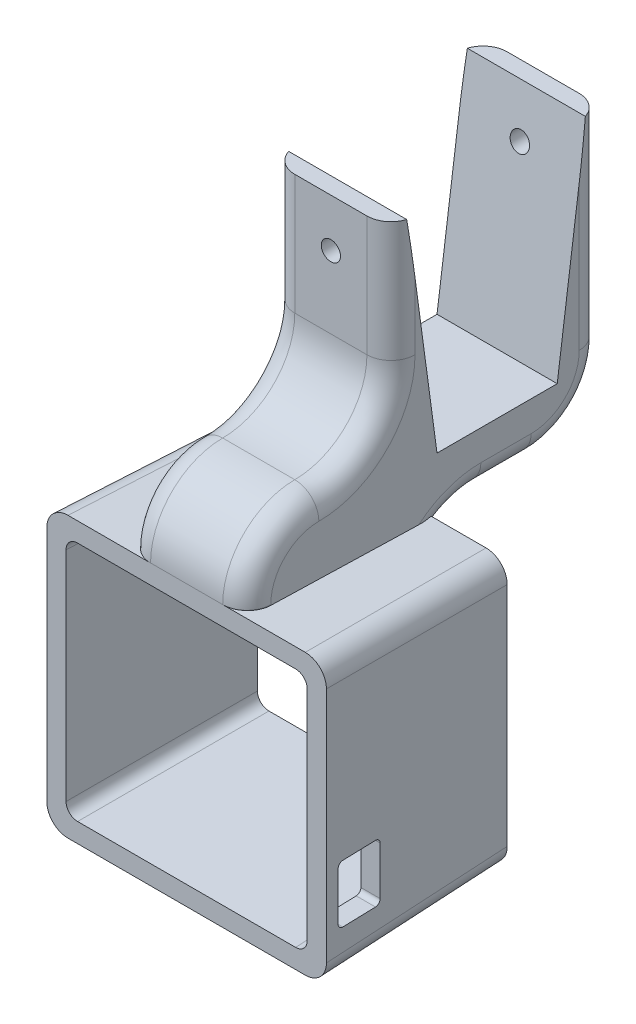
SolidWorks part; units mm, degrees
ref_plane "Front Plane" through (0, 0, 0) normal (0, 0, 1) x (1, 0, 0)
ref_plane "Top Plane" through (0, 0, 0) normal (0, 1, 0) x (1, 0, 0)
ref_plane "Right Plane" through (0, 0, 0) normal (1, 0, 0) x (0, 0, -1)
sketch "Sketch1" plane through (0, 0, 0) normal (0, 0, 1) x (1, 0, 0)
  line L0 (-27.975, -27.975) -> (-27.975, 27.975)
  line L1 (-23.975, -23.975) -> (23.975, -23.975)
  line L2 (-23.975, -23.975) -> (-23.975, 23.975)
  line L3 (-23.975, 23.975) -> (23.975, 23.975)
  line L4 (23.975, -23.975) -> (23.975, 23.975)
  line L5 (-23.975, -23.975) -> (23.975, 23.975) construction
  line L6 (-23.975, 23.975) -> (23.975, -23.975) construction
  line L7 (-27.975, 27.975) -> (27.975, 27.975)
  line L8 (27.975, -27.975) -> (27.975, 27.975)
  line L9 (-27.975, -27.975) -> (27.975, -27.975)
  point P0 (0, 0)
  dimension "D1" = 47.95
  dimension "D2" = 47.95
  dimension "D3" = 4
ref_plane "Plane1" through (0, 0, 38.7) normal (0, 0, 1) x (1, 0, 0)
sketch "Sketch2" plane through (0, 0, 38.7) normal (0, 0, 1) x (1, 0, 0)
  line L0 (-23.975, 23.975) -> (23.975, -23.975) construction
  line L1 (-25.075, -25.075) -> (25.075, -25.075)
  line L2 (-25.075, -25.075) -> (-25.075, 25.075)
  line L3 (-25.075, 25.075) -> (25.075, 25.075)
  line L4 (25.075, -25.075) -> (25.075, 25.075)
  line L5 (-25.075, -25.075) -> (25.075, 25.075) construction
  line L6 (-25.075, 25.075) -> (25.075, -25.075) construction
  line L7 (-29.075, 29.075) -> (29.075, 29.075)
  line L8 (29.075, -29.075) -> (29.075, 29.075)
  line L9 (-29.075, -29.075) -> (29.075, -29.075)
  line L10 (-29.075, -29.075) -> (-29.075, 29.075)
  point P0 (0, 0)
  dimension "D1" = 50.15
  dimension "D2" = 4
loft "Loft2" add section "Sketch1" section "Sketch2" connector at (-27.975, 27.975, 0) connector at (-29.075, 29.075, 38.7)
sketch "Sketch3" plane through (0, 0, 38.7) normal (0, 0, 1) x (1, 0, 0)
  line L14 (-25.075, -25.075) -> (25.075, -25.075)
  line L15 (25.075, -25.075) -> (25.075, 25.075)
  line L16 (25.075, 25.075) -> (-25.075, 25.075)
  line L17 (-25.075, 25.075) -> (-25.075, -25.075)
  line L18 (-25.075, -25.075) -> (25.075, -25.075)
  line L19 (25.075, -25.075) -> (25.075, 25.075)
  line L20 (25.075, 25.075) -> (-25.075, 25.075)
  line L21 (-25.075, 25.075) -> (-25.075, -25.075)
  dimension "D1" = 4
sketch "Sketch4" plane through (0, 0, 0) normal (0, 0, -1) x (-1, 0, 0)
  line L14 (-23.975, -23.975) -> (23.975, -23.975)
  line L15 (23.975, -23.975) -> (23.975, 23.975)
  line L16 (23.975, 23.975) -> (-23.975, 23.975)
  line L17 (-23.975, 23.975) -> (-23.975, -23.975)
  line L18 (-23.975, -23.975) -> (23.975, -23.975)
  line L19 (23.975, -23.975) -> (23.975, 23.975)
  line L20 (23.975, 23.975) -> (-23.975, 23.975)
  line L21 (-23.975, 23.975) -> (-23.975, -23.975)
  dimension "D1" = 4
loft "Cut-Loft1" cut profiles "Sketch4", "Sketch3" connector at (23.975, 23.975, 0) connector at (25.075, 25.075, 38.7)
fillet "Fillet1" radius 2.4 4 edges
fillet "Fillet2" radius 4.4 4 edges
sketch "Sketch5" plane through (0, 0, 0) normal (1, 0, 0) x (0, 0, -1)
  line L0 (-38.7, 31.9001) -> (-38.7, -31.9001) construction
  line L1 (-36.2, -8) -> (-27.2, -8)
  line L2 (-36.2, -8) -> (-36.2, -20)
  line L3 (-36.2, -20) -> (-27.2, -20)
  line L4 (-27.2, -8) -> (-27.2, -20)
  line L5 (-36.2, -8) -> (-27.2, -20) construction
  line L6 (-36.2, -20) -> (-27.2, -8) construction
  line L7 (-38.7, -29) -> (-47.7742, -29) construction
  point P0 (-31.7, -14)
  dimension "D1" = 2.5
  dimension "D2" = 11.5
  dimension "D3" = 29
  dimension "D4" = 9
  dimension "D5" = 21
extrude "Cut-Extrude1" cut sketch "Sketch5" along normal up to surface (28.7481 mm away) up to face at (28.525, -12.3384, 19.35)
fillet "Fillet3" radius 1 4 edges at (27.0039, -20, 36.2) (27.0039, -8, 36.2) (26.7481, -8, 27.2) (26.7481, -20, 27.2)
sketch "Sketch6" plane through (0, 0, 0) normal (1, 0, 0) x (0, 0, -1)
  line L0 (-38.7, 31.9826) -> (-38.7, -31.9826) construction
  line L1 (-8.7, 44.0797) -> (-8.7, 84.0797)
  line L2 (-8.7, 44.0797) -> (-38.7, 44.0797)
  line L3 (35.4525, 84.0797) -> (35.4525, 44.0797)
  line L4 (-38.7, 44.0797) -> (-38.7, 27.789)
  line L5 (0.8762, 39.0797) -> (25.8762, 39.0797)
  line L6 (-38.7, 27.789) -> (35.4525, 27.789)
  line L7 (0.8762, 39.0797) -> (-5.2, 84.0797)
  line L8 (35.4525, 27.789) -> (35.4525, 44.0797)
  line L10 (25.8762, 39.0797) -> (31.9525, 84.0797)
  line L11 (-8.7, 84.0797) -> (-5.2, 84.0797)
  line L12 (35.4525, 84.0797) -> (31.9525, 84.0797)
  dimension "D1" = 25
  dimension "D2" = 3.5
  dimension "D3" = 97.69
  dimension "D4" = 40
  dimension "D5" = 0
  dimension "D6" = 45
  dimension "D7" = 97.69
  dimension "D8" = 3.5
  dimension "D9" = 40
  dimension "D10" = 0
  dimension "D11" = 30
extrude "Boss-Extrude1" add sketch "Sketch6" along normal blind 12.5 and the other way blind 12.5
fillet "Fillet4" radius 15 4 edges at (0, 44.0797, 8.7) (0, 44.0797, 38.7) (0, 27.789, -35.4525) (0, 27.789, 0)
sketch "Sketch8" plane through (0, 0, 8.7) normal (0, 0, 1) x (1, 0, 0)
  line L0 (-12.5, 84.0797) -> (12.5, 84.0797) construction
  circle A0 centre (0, 74.0797) radius 2
  dimension "D2" = 4
  dimension "D1" = 10
extrude "Cut-Extrude2" cut sketch "Sketch8" against normal through all
fillet "Fillet7" radius 5 16 edges at (-12.5, 63.4343, -35.4525) (-12.5, 26.8031, -4.6453) (-12.5, 27.789, -15.2231) (12.5, 26.8031, -4.6453) (12.5, 27.789, -15.2231) (12.5, 63.4343, -35.4525) (-12.5, 39.6863, 34.3066) (-12.5, 71.5797, 8.7) (12.5, 71.5797, 8.7) (12.5, 39.6863, 34.3066) (-12.5, 32.1824, -31.0591) (12.5, 32.1824, -31.0591) (-12.5, 48.4731, 13.0934) (12.5, 48.4731, 13.0934)
